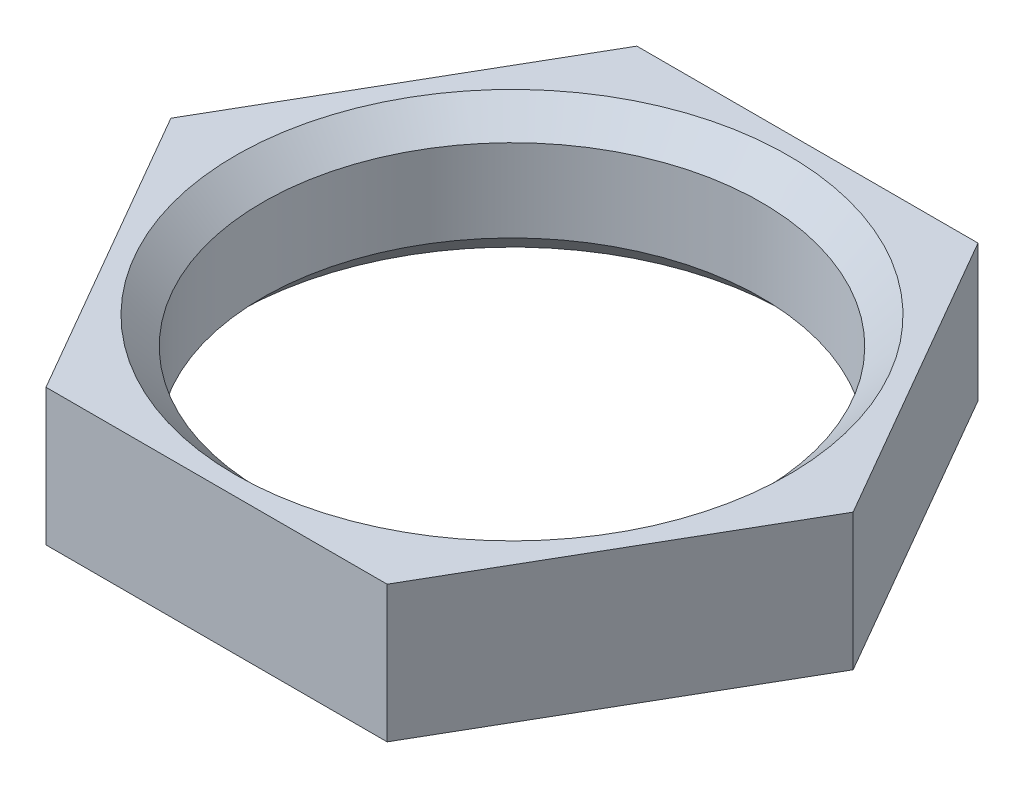
SolidWorks part; units mm, degrees
ref_plane "Front Plane" through (0, 0, 0) normal (0, 0, 1) x (1, 0, 0)
ref_plane "Top Plane" through (0, 0, 0) normal (0, 1, 0) x (1, 0, 0)
ref_plane "Right Plane" through (0, 0, 0) normal (1, 0, 0) x (0, 0, -1)
sketch "Sketch4" plane through (0, 0, 0) normal (0, 1, 0) x (1, 0, 0)
  line L1 (6.4085, 0) -> (3.2042, 5.5499)
  line L2 (3.2042, 5.5499) -> (-3.2042, 5.5499)
  line L3 (-3.2042, 5.5499) -> (-6.4085, 0)
  line L4 (-6.4085, 0) -> (-3.2042, -5.5499)
  line L5 (-3.2042, -5.5499) -> (3.2042, -5.5499)
  line L6 (3.2042, -5.5499) -> (6.4085, 0)
  circle A0 centre (0, 0) radius 5.5499 construction
  circle A1 centre (0, 0) radius 5.5499 construction
  circle A2 centre (0, 0) radius 5.5499 construction
  dimension "D1" = 11.0998
extrude "Boss-Extrude1" add sketch "Sketch4" along normal blind 2.5654
sketch "Sketch7" plane through (0, 2.5654, 0) normal (0, 1, 0) x (1, 0, 0)
  circle A0 centre (0, 0) radius 4.6863
  dimension "D1" = 9.3726
extrude "Cut-Extrude1" cut sketch "Sketch7" against normal through all
fillet "Fillet1" radius 0.508 1 edges at (0, 2.5654, 4.6863) profile chamfer
fillet "Fillet2" radius 0.508 1 edges at (0, 0, 4.6863) profile chamfer
sketch "Sketch12" plane through (0, 0, 0) normal (0, -1, 0) x (1, 0, 0)
  line L0 (3.2042, -5.5499) -> (-3.2042, -5.5499) construction
  line L1 (-3.2042, -5.5499) -> (-6.4085, 0) construction
  circle A0 centre (0, 0) radius 5.5499
